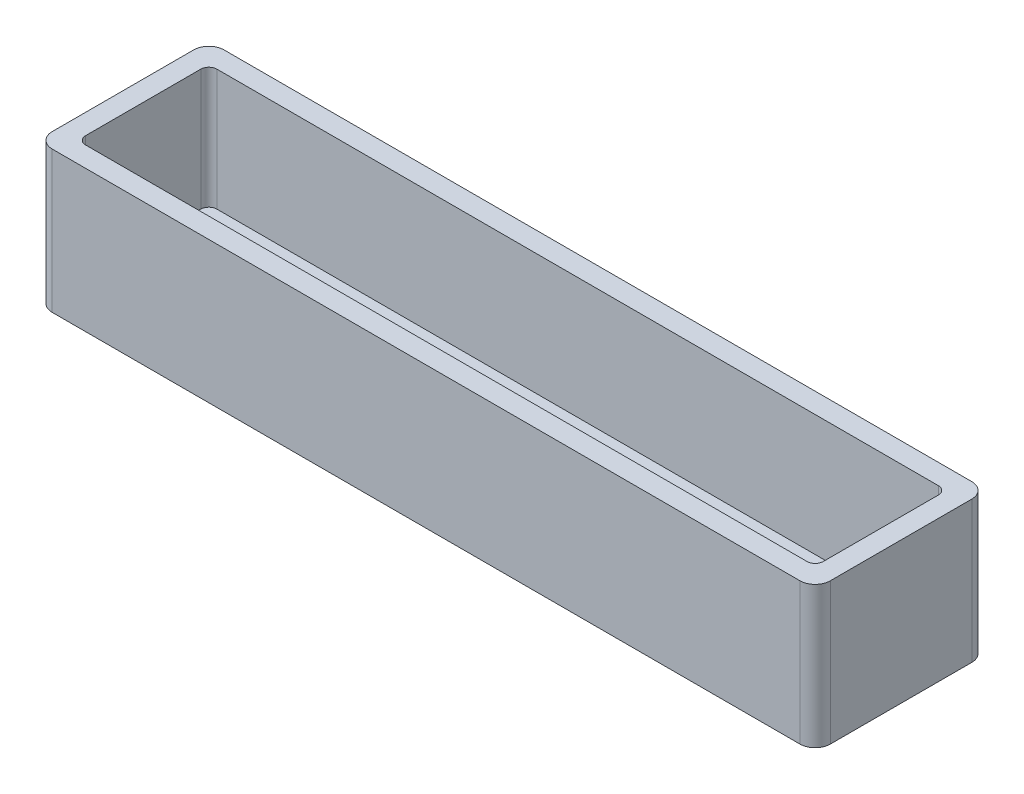
SolidWorks part; units mm, degrees
material "NEOPRENE"
ref_plane "Front" through (0, 0, 0) normal (0, 0, 1) x (1, 0, 0)
ref_plane "Top" through (0, 0, 0) normal (0, 1, 0) x (1, 0, 0)
ref_plane "Right" through (0, 0, 0) normal (1, 0, 0) x (0, 0, -1)
sketch "Sketch1" plane through (0, 0, 0) normal (0, 1, 0) x (1, 0, 0)
  line L0 (-115.8875, 0) -> (-122.2375, 0) construction
  line L1 (-122.2375, 26.9875) -> (122.2375, 26.9875)
  line L2 (-122.2375, 26.9875) -> (-122.2375, -26.9875)
  line L3 (-122.2375, -26.9875) -> (122.2375, -26.9875)
  line L4 (122.2375, 26.9875) -> (122.2375, -26.9875)
  line L5 (-122.2375, 26.9875) -> (122.2375, -26.9875) construction
  line L6 (-122.2375, -26.9875) -> (122.2375, 26.9875) construction
  line L7 (115.8875, 20.6375) -> (-115.8875, 20.6375)
  line L8 (115.8875, 20.6375) -> (115.8875, -20.6375)
  line L9 (115.8875, -20.6375) -> (-115.8875, -20.6375)
  line L10 (-115.8875, 20.6375) -> (-115.8875, -20.6375)
  line L11 (115.8875, 20.6375) -> (-115.8875, -20.6375) construction
  line L12 (115.8875, -20.6375) -> (-115.8875, 20.6375) construction
  line L13 (0, 20.6375) -> (0, 26.9875) construction
  point P0 (0, 0)
  point P6 (0, 0)
  dimension "D1" = 231.775
  dimension "D2" = 41.275
  dimension "D3" = 6.35
  dimension "THICKNESS" = 6.35
extrude "Boss-Extrude1" add sketch "Sketch1" along normal blind 38.1
sketch "Sketch2" plane through (0, 0, 0) normal (0, -1, 0) x (1, 0, 0)
  line L0 (104.4, 0) -> (73.4, 0) construction
  line L4 (122.2375, -26.9875) -> (122.2375, 26.9875)
  line L5 (122.2375, 26.9875) -> (-122.2375, 26.9875)
  line L6 (-122.2375, 26.9875) -> (-122.2375, -26.9875)
  line L7 (-122.2375, -26.9875) -> (122.2375, -26.9875)
  line L8 (122.2375, -26.9875) -> (122.2375, 26.9875)
  line L9 (122.2375, 26.9875) -> (-122.2375, 26.9875)
  line L10 (-122.2375, 26.9875) -> (-122.2375, -26.9875)
  line L11 (-122.2375, -26.9875) -> (122.2375, -26.9875)
  arc A0 (104.4, -2.1) -> (104.4, 2.1) centre (104.4, 0) ccw construction
  arc A1 (104.4, 2.1) -> (104.4, -2.1) centre (104.4, 0) ccw construction
  arc A2 (73.4, -2.1) -> (73.4, 2.1) centre (73.4, 0) ccw construction
  arc A3 (73.4, 2.1) -> (73.4, -2.1) centre (73.4, 0) ccw construction
  arc A4 (104.4, -2.1) -> (104.4, 2.1) centre (104.4, 0) ccw
  arc A5 (104.4, 2.1) -> (104.4, -2.1) centre (104.4, 0) ccw
  arc A6 (73.4, -2.1) -> (73.4, 2.1) centre (73.4, 0) ccw
  arc A7 (73.4, 2.1) -> (73.4, -2.1) centre (73.4, 0) ccw
  circle A8 centre (88.9, 0) radius 12.065
  dimension "D2" = 24.13
  dimension "D1" = 0
extrude "Boss-Extrude2" add sketch "Sketch2" along normal blind 6.35
fillet "Fillet1" radius 2.54 4 edges at (115.8875, 19.05, -20.6375) (115.8875, 19.05, 20.6375) (-115.8875, 19.05, 20.6375) (-115.8875, 19.05, -20.6375)
fillet "Fillet2" radius 4.7625 4 edges at (-122.2375, 15.875, -26.9875) (122.2375, 15.875, -26.9875) (122.2375, 15.875, 26.9875) (-122.2375, 15.875, 26.9875)
sketch "Sketch6" [suppressed] plane through (0, -6.35, 0) normal (0, -1, 0) x (1, 0, 0)
  circle A0 centre (73.4, 0) radius 2.1 construction
  circle A1 centre (73.4, 0) radius 2.1
  circle A2 centre (104.4, 0) radius 2.1 construction
  circle A3 centre (104.4, 0) radius 2.1
extrude "Boss-Extrude4" [suppressed] add sketch "Sketch6" against normal up to surface (6.35 mm away) up to face at (73.4, 0, -2.1)
sketch "Sketch7" [suppressed] plane through (0, -6.35, 0) normal (0, -1, 0) x (1, 0, 0)
  circle A0 centre (-45.2, 0.936) radius 4.445
  circle A1 centre (45, 0.936) radius 4.445
  dimension "D1" = 8.89
extrude "Cut-Extrude3" [suppressed] cut sketch "Sketch7" against normal through all
sketch "Sketch8" [suppressed] plane through (0, 38.1, 0) normal (0, 1, 0) x (1, 0, 0)
  line L25 (-156.7727, 50.8) -> (156.7727, 50.8)
  line L26 (-156.7727, 50.8) -> (-156.7727, -50.8)
  line L27 (-156.7727, -50.8) -> (156.7727, -50.8)
  line L28 (156.7727, 50.8) -> (156.7727, -50.8)
  line L29 (-156.7727, 50.8) -> (156.7727, -50.8) construction
  line L30 (-156.7727, -50.8) -> (156.7727, 50.8) construction
  point P15 (0, 0)
  dimension "D2" = 101.6
  dimension "D1" = 313.5454
extrude "Cut-Extrude4" [suppressed] cut sketch "Sketch8" against normal blind 9.525
equation "\"D1@Boss-Extrude2\"=\"THICKNESS\""
